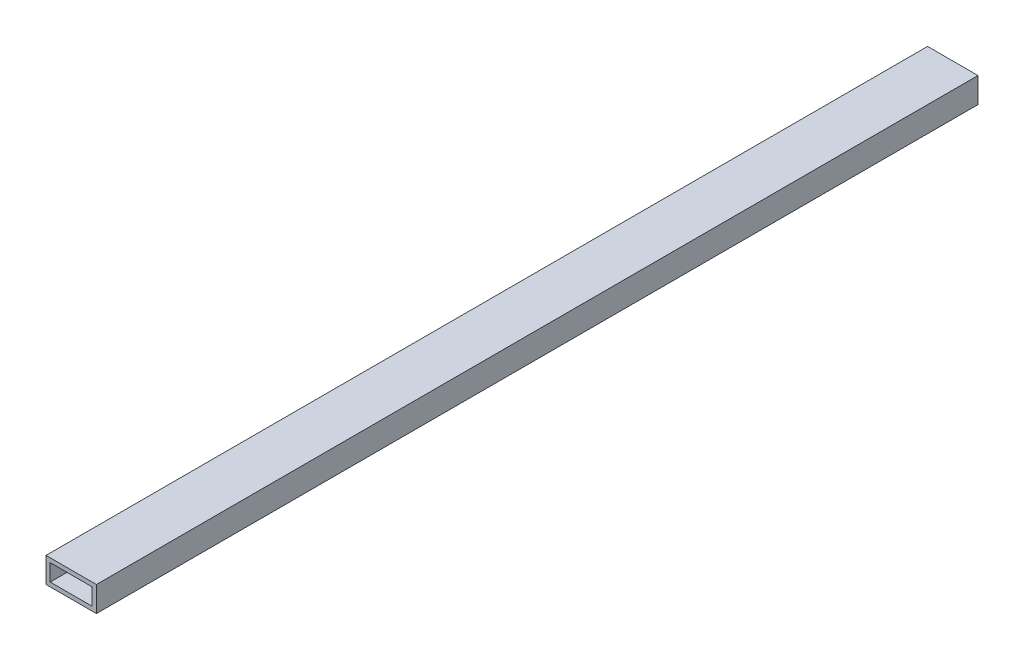
SolidWorks part; units mm, degrees
ref_plane "Front" through (0, 0, 0) normal (0, 0, 1) x (1, 0, 0)
ref_plane "Top" through (0, 0, 0) normal (0, 1, 0) x (1, 0, 0)
ref_plane "Right" through (0, 0, 0) normal (1, 0, 0) x (0, 0, -1)
sketch "Sketch2" plane through (0, 0, 0) normal (0, 0, 1) x (1, 0, 0)
  line L1 (-29.3091, 14.9139) -> (8.7909, 14.9139)
  line L2 (-29.3091, 14.9139) -> (-29.3091, -4.1361)
  line L3 (-29.3091, -4.1361) -> (8.7909, -4.1361)
  line L4 (8.7909, 14.9139) -> (8.7909, -4.1361)
  dimension "D1" = 38.1
  dimension "D2" = 19.05
extrude "Boss-Extrude1" add sketch "Sketch2" along normal blind 666.242 contours L4 L3 L2 L1
sketch "Sketch4" plane through (0, 0, 0) normal (0, 0, -1) x (-1, 0, 0)
  line L8 (26.1341, 11.7389) -> (-5.6159, 11.7389)
  line L9 (-5.6159, 11.7389) -> (-5.6159, -0.9611)
  line L10 (-5.6159, -0.9611) -> (26.1341, -0.9611)
  line L11 (26.1341, -0.9611) -> (26.1341, 11.7389)
  line L12 (26.1341, 11.7389) -> (-5.6159, 11.7389)
  line L13 (-5.6159, 11.7389) -> (-5.6159, -0.9611)
  line L14 (-5.6159, -0.9611) -> (26.1341, -0.9611)
  line L15 (26.1341, -0.9611) -> (26.1341, 11.7389)
  dimension "D1" = 3.175
extrude "Cut-Extrude1" cut sketch "Sketch4" against normal through all
